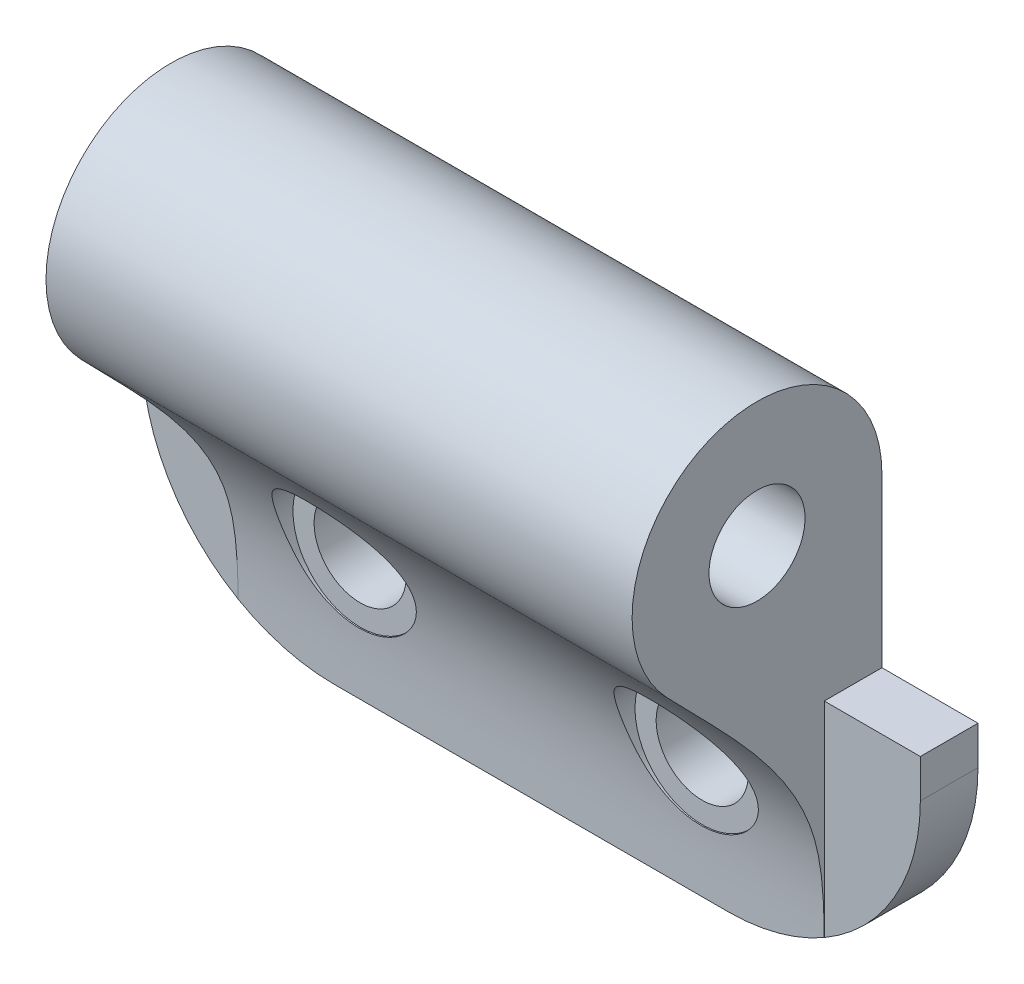
SolidWorks part; units mm, degrees
material "AISI 1045 钢，冷拔"
ref_plane "前视基准面" through (0, 0, 0) normal (0, 0, 1) x (1, 0, 0)
ref_plane "上视基准面" through (0, 0, 0) normal (0, 1, 0) x (1, 0, 0)
ref_plane "右视基准面" through (0, 0, 0) normal (1, 0, 0) x (0, 0, -1)
sketch "草图1" plane through (0, 0, 0) normal (0, 0, 1) x (1, 0, 0)
  line L1 (-20.25, 6) -> (20.25, 6)
  line L2 (-20.25, 6) -> (-20.25, -6)
  line L3 (-20.25, -6) -> (20.25, -6)
  line L4 (20.25, 6) -> (20.25, -6)
  line L5 (-20.25, 6) -> (20.25, -6) construction
  line L6 (-20.25, -6) -> (20.25, 6) construction
  point P0 (0, 0)
  dimension "D1" = 40.5
  dimension "D2" = 12
extrude "凸台-拉伸1" add sketch "草图1" along normal blind 3
sketch "草图2" plane through (0, 0, 0) normal (1, 0, 0) x (0, 0, -1)
  line L0 (0, -6) -> (0, 14.75)
  line L1 (0, -6) -> (0, 6) construction
  line L4 (-3, -6) -> (-3, 6) construction
  line L5 (-3, -6) -> (0, -6)
  arc A0 (0, 14.75) -> (-11.195, 10.2548) centre (-6.5, 14.75) ccw
  circle A1 centre (-6.5, 14.75) radius 2.5
  spline S0 degree 3 poles (-3, -6) (-3, -3.8347) (-2.9492, 2.4308) (-8.1131, 7.0359) (-11.195, 10.2548) knots 0 0 0 0 0.319547 1 1 1 1
  dimension "D1" = 13
  dimension "D2" = 5
  dimension "D3" = 0.5
  dimension "D4" = 20.75
extrude "凸台-拉伸2" add sketch "草图2" along normal mid plane 30.5
sketch "草图3" plane through (0, 0, 0) normal (0, 0, -1) x (-1, 0, 0)
  line L1 (-15.25, 14.75) -> (15.25, 14.75) construction
  circle A0 centre (-8.9, 0.75) radius 2.4
  dimension "D1" = 4.8
  dimension "D2" = 14
  dimension "D3" = 8.9
extrude "切除-拉伸1" cut sketch "草图3" against normal blind 30.5
mirror "镜向1" about plane through (0, 0, 0) normal (1, 0, 0) of "切除-拉伸1"
fillet "圆角1" radius 10 2 edges at (20.25, -6, 1.5) (-20.25, -6, 1.5)
sketch "草图4" plane through (0, 0, 3) normal (0, 0, 1) x (1, 0, 0)
  circle A0 centre (-8.9, 0.75) radius 3.5
  dimension "D1" = 7
extrude "切除-拉伸2" cut sketch "草图4" along normal blind 30.5
mirror "镜向2" about plane through (0, 0, 0) normal (1, 0, 0) of "切除-拉伸2"
